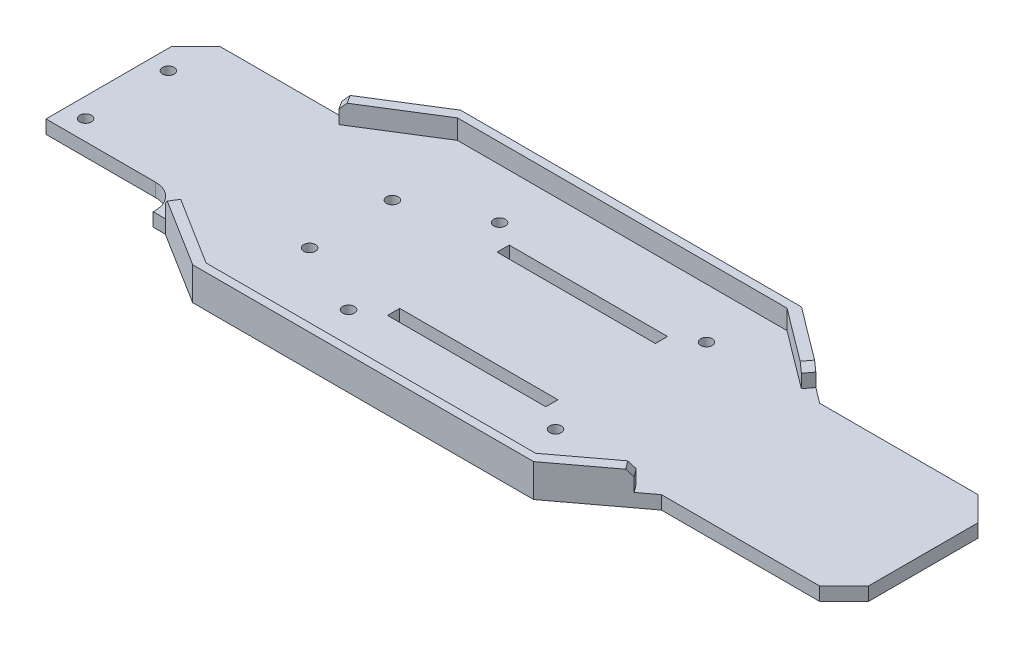
SolidWorks part; units mm, degrees
material "PETG - Polymaker"
ref_plane "Front Plane" through (0, 0, 0) normal (0, 0, 1) x (1, 0, 0)
ref_plane "Top Plane" through (0, 0, 0) normal (0, 1, 0) x (1, 0, 0)
ref_plane "Right Plane" through (0, 0, 0) normal (1, 0, 0) x (0, 0, -1)
sketch "Sketch1" plane through (0, 0, 0) normal (0, 1, 0) x (1, 0, 0)
  line L0 (-235.1499, 0) -> (235.1499, 0) construction
  line L1 (0, 0) -> (0, 52596.8311) construction
  line L2 (-100, 36.25) -> (-70, 55)
  line L3 (-70, 55) -> (70, 55)
  line L4 (-100, 36.25) -> (-160, 36.25)
  line L5 (-160, 36.25) -> (-160, -36.25)
  line L6 (-70, -55) -> (70, -55)
  line L7 (-100, -36.25) -> (-70, -55)
  line L8 (-100, -36.25) -> (-160, -36.25)
  line L9 (70, 55) -> (100, 32.5)
  line L10 (100, 32.5) -> (175, 32.5)
  line L11 (175, 32.5) -> (175, -32.5)
  line L12 (100, -32.5) -> (175, -32.5)
  line L13 (70, -55) -> (100, -32.5)
  point P3 (0, 0)
  point P10 (-85, 45.625)
  point P15 (-85, -45.625)
  point P18 (-160, 0)
  point P19 (0, -55)
  point P20 (0, 55)
  point P23 (175, 0)
  dimension "D1" = 55
  dimension "D2" = 72.5
  dimension "D3" = 30
  dimension "D4" = 60
  dimension "D5" = 140
  dimension "D6" = 75
  dimension "D7" = 65
  dimension "D8" = 30
  dimension "D9" = 110
extrude "Boss-Extrude1" add sketch "Sketch1" along normal blind 5.5
sketch "Sketch3" plane through (0, 5.5, 0) normal (0, 1, 0) x (1, 0, 0)
  line L0 (0, 0) -> (50000, 0) construction
  line L1 (0, 0) -> (0, 50000) construction
  line L2 (0, 55) -> (-70, 55)
  line L3 (70, 55) -> (-70, 55) construction
  line L4 (-70, 55) -> (-100, 36.25)
  line L5 (-100, 36.25) -> (-97.88, 32.858)
  line L6 (-97.88, 32.858) -> (-67.88, 51.608)
  line L7 (-67.88, 51.608) -> (0, 51.608)
  line L8 (-70, 55) -> (-67.88, 51.608) construction
  line L9 (0, 55) -> (70, 55)
  line L10 (70, 55) -> (93.6, 37.3)
  line L11 (93.6, 37.3) -> (91.056, 33.908)
  line L12 (91.056, 33.908) -> (67.456, 51.608)
  line L13 (67.456, 51.608) -> (0, 51.608)
  line L14 (67.456, 51.608) -> (70, 55) construction
  line L15 (67.456, -51.608) -> (70, -55) construction
  line L16 (-70, -55) -> (-67.88, -51.608) construction
  line L27 (-70, 55) -> (-100, 36.25) construction
  line L28 (100, 32.5) -> (70, 55) construction
  line L29 (67.456, -51.608) -> (0, -51.608)
  line L30 (91.056, -33.908) -> (67.456, -51.608)
  line L31 (93.6, -37.3) -> (91.056, -33.908)
  line L32 (70, -55) -> (93.6, -37.3)
  line L33 (0, -55) -> (70, -55)
  line L34 (-67.88, -51.608) -> (0, -51.608)
  line L35 (-97.88, -32.858) -> (-67.88, -51.608)
  line L36 (-100, -36.25) -> (-97.88, -32.858)
  line L37 (-70, -55) -> (-100, -36.25)
  line L38 (0, -55) -> (-70, -55)
  dimension "D1" = 4
  dimension "D2" = 0
  dimension "D3" = 8
extrude "Chassis-Walls1" add sketch "Sketch3" along normal blind 8
chamfer "Chamfer1" distance 10 angle 45 2 edges at (-160, 2.75, -36.25) (-160, 2.75, 36.25)
chamfer "Chamfer2" distance 10 angle 45 2 edges at (175, 2.75, -32.5) (175, 2.75, 32.5)
chamfer "Chamfer3" distance 2.5 angle 45 4 edges at (-98.94, 13.5, -34.554) (92.328, 13.5, -35.604) (-98.94, 13.5, 34.554) (92.328, 13.5, 35.604)
sketch "Sketch4" plane through (0, 0, 0) normal (0, -1, 0) x (1, 0, 0)
  line L0 (0, 0) -> (50000, 0) construction
  line L1 (-152, 17) -> (-60, 17) construction
  line L2 (-160, -26.25) -> (-160, 26.25) construction
  circle A0 centre (-152, 17) radius 2.4
  circle A1 centre (-60, 17) radius 2.4
  circle A2 centre (-60, -17) radius 2.4
  circle A3 centre (-152, -17) radius 2.4
  circle A4 centre (-30, 31) radius 2.4
  circle A5 centre (55, 31) radius 2.4
  circle A6 centre (55, -31) radius 2.4
  circle A7 centre (-30, -31) radius 2.4
  dimension "D1" = 4.8
  dimension "D2" = 4.8
  dimension "D6" = 4.8
  dimension "D8" = 4.8
  dimension "D3" = 8
  dimension "D4" = 92
  dimension "D5" = 34
  dimension "D7" = 30
  dimension "D9" = 85
  dimension "D10" = 62
extrude "Cut-Extrude1" cut sketch "Sketch4" against normal blind 10
sketch "Sketch5" plane through (0, 5.5, 0) normal (0, 1, 0) x (1, 0, 0)
  line L0 (-160, -25.25) -> (-105, -25.25)
  line L1 (-160, 26.25) -> (-160, -26.25) construction
  line L2 (-105, -25.25) -> (-105, -36.25)
  line L3 (-150, -36.25) -> (-100, -36.25) construction
  line L4 (-105, -36.25) -> (-160, -36.25)
  line L5 (-160, -36.25) -> (-160, -25.25)
  dimension "D1" = 55
  dimension "D2" = 11
extrude "Cut-Extrude2" cut sketch "Sketch5" against normal blind 10
sketch "Sketch6" plane through (0, 5.5, 0) normal (0, 1, 0) x (1, 0, 0)
  line L0 (0, 0) -> (50000, 0) construction
  line L1 (55, 31) -> (-30, 31) construction
  line L2 (12.5, 30.75) -> (12.5, 50030.75) construction
  line L3 (-20, -20) -> (45, -25) construction
  line L4 (-20, 25) -> (45, 25)
  line L5 (-20, 25) -> (-20, 20)
  line L6 (-20, 20) -> (45, 20)
  line L7 (45, 25) -> (45, 20)
  line L8 (-20, 25) -> (45, 20) construction
  line L9 (-20, 20) -> (45, 25) construction
  line L10 (-20, -25) -> (45, -20) construction
  line L11 (45, -25) -> (45, -20)
  line L12 (-20, -20) -> (45, -20)
  line L13 (-20, -25) -> (-20, -20)
  line L14 (-20, -25) -> (45, -25)
  point P9 (12.5, 31)
  point P10 (12.5, 22.5)
  point P19 (12.5, -22.5)
  dimension "D1" = 5
  dimension "D2" = 65
  dimension "D3" = 20
extrude "Cut-Extrude3" cut sketch "Sketch6" against normal through all
fillet "Fillet1" radius 10 1 edges at (-105, 2.75, 25.25)
equation "\"D6@Sketch4\"=\"D2@Sketch4\""
equation "\"D8@Sketch4\"=\"D2@Sketch4\""
